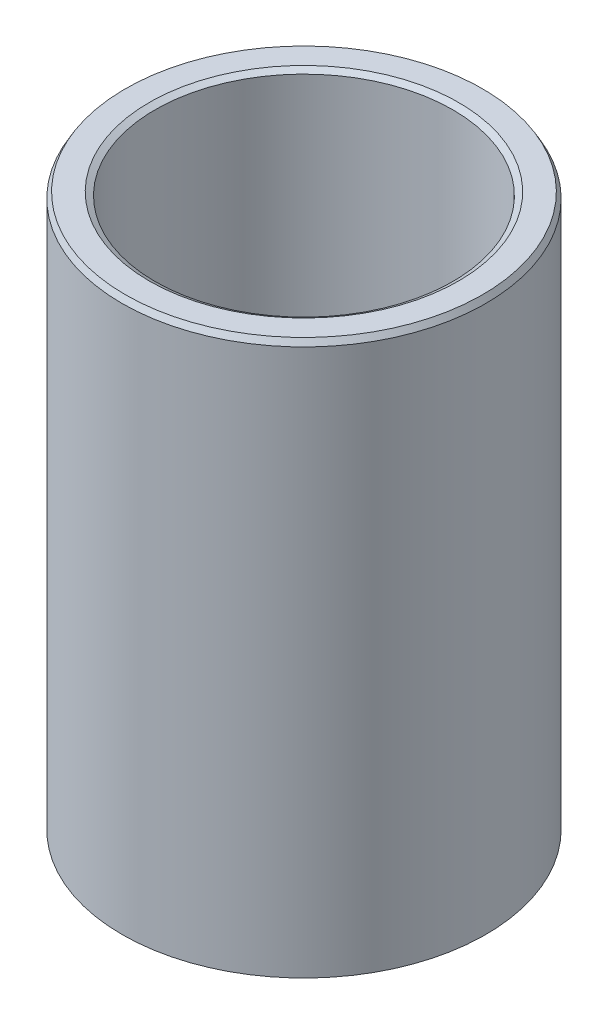
SolidWorks part; units mm, degrees
ref_plane "Front Plane" through (0, 0, 0) normal (0, 0, 1) x (1, 0, 0)
ref_plane "Top Plane" through (0, 0, 0) normal (0, 1, 0) x (1, 0, 0)
ref_plane "Right Plane" through (0, 0, 0) normal (1, 0, 0) x (0, 0, -1)
sketch "Sketch1" plane through (0, 0, 0) normal (0, 1, 0) x (1, 0, 0)
  circle A0 centre (0, 0) radius 42.5
  dimension "SLEEVE_OD" = 85
extrude "Boss-Extrude1" add sketch "Sketch1" along normal blind 129.8739
sketch "Sketch2" plane through (0, 0, 0) normal (0, 1, 0) x (1, 0, 0)
  circle A0 centre (0, 0) radius 34.7826
  dimension "BORE_D" = 69.5652
extrude "Cut-Extrude1" cut sketch "Sketch2" along normal through all
chamfer "Chamfer1" distance 1.3643 angle 30 4 edges at (0, 129.8739, 34.7826) (0, 0, 34.7826) (0, 0, 42.5) (0, 129.8739, 42.5) first distance on face at (0, 129.8739, 34.7826) first distance on face at (0, 0, 34.7826) first distance on face at (0, 129.8739, 42.5)
